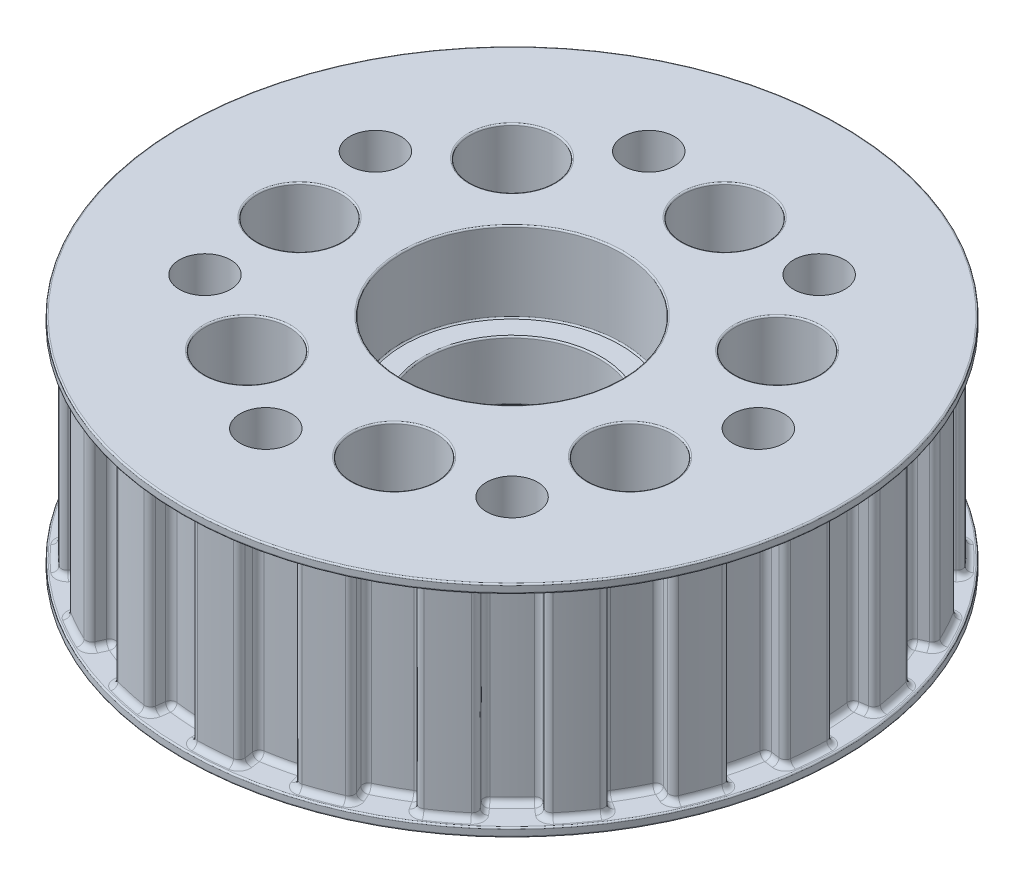
SolidWorks part; units mm, degrees
material "Aluminiumoxid"
ref_plane "Ebene vorne" through (0, 0, 0) normal (0, 0, 1) x (1, 0, 0)
ref_plane "Ebene oben" through (0, 0, 0) normal (0, 1, 0) x (1, 0, 0)
ref_plane "Ebene rechts" through (0, 0, 0) normal (1, 0, 0) x (0, 0, -1)
sketch "Skizze1" plane through (0, 0, 0) normal (0, 1, 0) x (1, 0, 0)
  circle A0 centre (0, 0) radius 45
  dimension "D1" = 90
extrude "Aufsatz-Linear austragen1" add sketch "Skizze1" along normal mid plane 30
sketch "Skizze2" plane through (0, 15, 0) normal (0, 1, 0) x (1, 0, 0)
  circle A0 centre (0, 0) radius 15
  dimension "D1" = 30
extrude "Schnitt-Linear austragen1" cut sketch "Skizze2" against normal blind 10.925
mirror "Spiegeln1" about plane through (0, 0, 0) normal (0, 1, 0) of "Schnitt-Linear austragen1"
sketch "Skizze3" plane through (0, -4.075, 0) normal (0, -1, 0) x (1, 0, 0)
  circle A0 centre (0, 0) radius 11.9
  dimension "D1" = 23.8
extrude "Schnitt-Linear austragen2" cut sketch "Skizze3" against normal through all
ref_plane "Ebene1" through (0, 13.8, 0) normal (0, 1, 0) x (1, 0, 0)
sketch "Skizze4" plane through (0, 13.8, 0) normal (0, 1, 0) x (1, 0, 0)
  line L0 (0, 0) -> (0, 50.5157) construction
  line L1 (0, 0) -> (7.4496, 51.8134) construction
  line L2 (0, 47.0395) -> (0, 41)
  line L3 (6.6944, 46.5607) -> (5.8349, 40.5827)
  arc A0 (5.8349, 40.5827) -> (0, 41) centre (0, 0) ccw
  circle A1 centre (0, 0) radius 45 construction
  arc A2 (6.6944, 46.5607) -> (0, 47.0395) centre (0, 0) ccw
  dimension "D1" = 8.182
  dimension "D2" = 4
extrude "Schnitt-Linear austragen3" cut sketch "Skizze4" against normal blind 27.6
pattern_circular "Kreismuster1" count 22 over 360 about axis through (0, 0, 0) along (0, 1, 0) of "Schnitt-Linear austragen3"
sketch "Skizze6" plane through (0, 13.8, 0) normal (0, 1, 0) x (1, 0, 0)
  circle A0 centre (0, 0) radius 55.1109
  circle A1 centre (0, 0) radius 43.8
  circle A2 centre (0, 0) radius 45 construction
  dimension "D1" = 110.2218
  dimension "D3" = 1.2
extrude "Schnitt-Linear austragen5" cut sketch "Skizze6" against normal blind 27.6
fillet "Verrundung1" radius 0.8 264 edges at (37.2949, 0, 17.032) (35.6691, -13.8, 22.9232) (35.6691, 13.8, 22.9232) (35.9848, 13.8, 19.6492) (35.9848, -13.8, 19.6492) (34.4914, 0, 22.1663) (30.9857, 0, 26.8493) (27.7661, -13.8, 32.0438) (27.7661, 13.8, 32.0438) (28.9914, 13.8, 28.9914) (28.9914, -13.8, 28.9914) (26.8493, 0, 30.9857) (22.1663, 0, 34.4914) (17.6136, -13.8, 38.5684) (17.6136, 13.8, 38.5684) (19.6492, 13.8, 35.9848) (19.6492, -13.8, 35.9848) (17.032, 0, 37.2949) (11.551, 0, 39.3392) (6.0341, -13.8, 41.9684) (6.0341, 13.8, 41.9684) (8.7152, 13.8, 40.063) (8.7152, -13.8, 40.063) (5.8349, 0, 40.5827) (0, 0, 41) (-6.0341, -13.8, 41.9684) (-6.0341, 13.8, 41.9684) (-2.9249, 13.8, 40.8955) (-2.9249, -13.8, 40.8955) (-5.8349, 0, 40.5827) (-11.551, 0, 39.3392) (-17.6136, -13.8, 38.5684) (-17.6136, 13.8, 38.5684) (-14.328, 13.8, 38.4149) (-14.328, -13.8, 38.4149) (-17.032, 0, 37.2949) (-22.1663, 0, 34.4914) (-27.7661, -13.8, 32.0438) (-27.7661, 13.8, 32.0438) (-24.5704, 13.8, 32.8222) (-24.5704, -13.8, 32.8222) (-26.8493, 0, 30.9857) (-30.9857, 0, 26.8493) (-35.6691, -13.8, 22.9232) (-35.6691, 13.8, 22.9232) (-32.8222, 13.8, 24.5704) (-32.8222, -13.8, 24.5704) (-34.4914, 0, 22.1663) (-37.2949, 0, 17.032) (-40.6825, -13.8, 11.9455) (-40.6825, 13.8, 11.9455) (-38.4149, 13.8, 14.328) (-38.4149, -13.8, 14.328) (-39.3392, 0, 11.551) (-40.5827, 0, 5.8349) (-42.4, -13.8, 0) (-42.4, 13.8, 0) (-40.8955, 13.8, 2.9249) (-40.8955, -13.8, 2.9249) (-41, 0, 0) (-40.5827, 0, -5.8349) (-40.6825, -13.8, -11.9455) (-40.6825, 13.8, -11.9455) (-40.063, 13.8, -8.7152) (-40.063, -13.8, -8.7152) (-39.3392, 0, -11.551) (-37.2949, 0, -17.032) (-35.6691, -13.8, -22.9232) (-35.6691, 13.8, -22.9232) (-35.9848, 13.8, -19.6492) (-35.9848, -13.8, -19.6492) (-34.4914, 0, -22.1663) (-30.9857, 0, -26.8493) (-27.7661, -13.8, -32.0438) (-27.7661, 13.8, -32.0438) (-28.9914, 13.8, -28.9914) (-28.9914, -13.8, -28.9914) (-26.8493, 0, -30.9857) (-22.1663, 0, -34.4914) (-17.6136, -13.8, -38.5684) (-17.6136, 13.8, -38.5684) (-19.6492, 13.8, -35.9848) (-19.6492, -13.8, -35.9848) (-17.032, 0, -37.2949) (37.2949, 0, -17.032) (40.6825, -13.8, -11.9455) (40.6825, 13.8, -11.9455) (38.4149, 13.8, -14.328) (38.4149, -13.8, -14.328) (39.3392, 0, -11.551) (30.9857, 0, -26.8493) (35.6691, -13.8, -22.9232) (35.6691, 13.8, -22.9232) (32.8222, 13.8, -24.5704) (32.8222, -13.8, -24.5704) (34.4914, 0, -22.1663) (22.1663, 0, -34.4914) (27.7661, -13.8, -32.0438) (27.7661, 13.8, -32.0438) (24.5704, 13.8, -32.8222) (24.5704, -13.8, -32.8222) (26.8493, 0, -30.9857) (11.551, 0, -39.3392) (17.6136, -13.8, -38.5684) (17.6136, 13.8, -38.5684) (14.328, 13.8, -38.4149) (14.328, -13.8, -38.4149) (17.032, 0, -37.2949) (-11.551, 0, -39.3392) (-6.0341, -13.8, -41.9684) (-6.0341, 13.8, -41.9684) (-8.7152, 13.8, -40.063) (-8.7152, -13.8, -40.063) (-5.8349, 0, -40.5827) (0, 0, -41) (6.0341, -13.8, -41.9684) (6.0341, 13.8, -41.9684) (2.9249, 13.8, -40.8955) (2.9249, -13.8, -40.8955) (5.8349, 0, -40.5827) (41.9684, 13.8, -6.0341) (41.9684, -13.8, -6.0341) (41.9684, 13.8, 6.0341) (41.9684, -13.8, 6.0341) (38.5684, 13.8, 17.6136) (38.5684, -13.8, 17.6136) (32.0438, 13.8, 27.7661) (32.0438, -13.8, 27.7661) (22.9232, 13.8, 35.6691) (22.9232, -13.8, 35.6691) (11.9455, 13.8, 40.6825) (11.9455, -13.8, 40.6825) (0, 13.8, 42.4) (0, -13.8, 42.4) (-11.9455, 13.8, 40.6825) (-11.9455, -13.8, 40.6825) (-22.9232, 13.8, 35.6691) (-22.9232, -13.8, 35.6691) (-32.0438, 13.8, 27.7661) (-32.0438, -13.8, 27.7661) (-38.5684, 13.8, 17.6136) (-38.5684, -13.8, 17.6136) (-41.9684, 13.8, 6.0341) (-41.9684, -13.8, 6.0341) (-41.9684, 13.8, -6.0341) (-41.9684, -13.8, -6.0341) (-38.5684, 13.8, -17.6136) (-38.5684, -13.8, -17.6136) (-32.0438, 13.8, -27.7661) (-32.0438, -13.8, -27.7661) (-22.9232, 13.8, -35.6691) (-22.9232, -13.8, -35.6691) (38.5684, 13.8, -17.6136) (38.5684, -13.8, -17.6136) (32.0438, 13.8, -27.7661) (32.0438, -13.8, -27.7661) (22.9232, 13.8, -35.6691) (22.9232, -13.8, -35.6691) (11.9455, 13.8, -40.6825) (11.9455, -13.8, -40.6825) (-11.9455, 13.8, -40.6825) (-11.9455, -13.8, -40.6825) (0, 13.8, -42.4) (0, -13.8, -42.4) (15.3065, -13.8, 41.0384) (26.2484, -13.8, 35.0637) (35.0637, -13.8, 26.2484) (41.0384, -13.8, 15.3065) (43.6884, -13.8, 3.1247) (42.799, -13.8, -9.3104) (38.4423, -13.8, -20.9911) (30.9713, -13.8, -30.9713) (20.9911, -13.8, -38.4423) (9.3104, -13.8, -42.799) (-3.1247, -13.8, -43.6884) (-15.3065, -13.8, -41.0384) (-26.2484, -13.8, -35.0637) (-35.0637, -13.8, -26.2484) (-41.0384, -13.8, -15.3065) (-43.6884, -13.8, -3.1247) (-42.799, -13.8, 9.3104) (-38.4423, -13.8, 20.9911) (-30.9713, -13.8, 30.9713) (-20.9911, -13.8, 38.4423) (-9.3104, -13.8, 42.799) (3.1247, -13.8, 43.6884) (-3.1247, 13.8, -43.6884) (9.3104, 13.8, -42.799) (-15.3065, 13.8, -41.0384) (0, 0, -43.8) (6.2334, 0, -43.3542) (-12.3399, 0, -42.0258) (-6.2334, 0, -43.3542) (20.9911, 13.8, -38.4423) (12.3399, 0, -42.0258) (18.1952, 0, -39.8419) (30.9713, 13.8, -30.9713) (23.6801, 0, -36.8469) (28.6829, 0, -33.1018) (38.4423, 13.8, -20.9911) (33.1018, 0, -28.6829) (36.8469, 0, -23.6801) (42.799, 13.8, -9.3104) (-26.2484, 13.8, -35.0637) (39.8419, 0, -18.1952) (42.0258, 0, -12.3399) (-35.0637, 13.8, -26.2484) (-23.6801, 0, -36.8469) (-18.1952, 0, -39.8419) (-41.0384, 13.8, -15.3065) (-33.1018, 0, -28.6829) (-28.6829, 0, -33.1018) (-43.6884, 13.8, -3.1247) (-39.8419, 0, -18.1952) (-36.8469, 0, -23.6801) (-42.799, 13.8, 9.3104) (-43.3542, 0, -6.2334) (-42.0258, 0, -12.3399) (-38.4423, 13.8, 20.9911) (-43.3542, 0, 6.2334) (-43.8, 0, 0) (-30.9713, 13.8, 30.9713) (-39.8419, 0, 18.1952) (-42.0258, 0, 12.3399) (-20.9911, 13.8, 38.4423) (-33.1018, 0, 28.6829) (-36.8469, 0, 23.6801) (-9.3104, 13.8, 42.799) (-23.6801, 0, 36.8469) (-28.6829, 0, 33.1018) (3.1247, 13.8, 43.6884) (-12.3399, 0, 42.0258) (-18.1952, 0, 39.8419) (15.3065, 13.8, 41.0384) (0, 0, 43.8) (-6.2334, 0, 43.3542) (26.2484, 13.8, 35.0637) (12.3399, 0, 42.0258) (6.2334, 0, 43.3542) (35.0637, 13.8, 26.2484) (23.6801, 0, 36.8469) (18.1952, 0, 39.8419) (41.0384, 13.8, 15.3065) (33.1018, 0, 28.6829) (28.6829, 0, 33.1018) (43.6884, 13.8, 3.1247) (39.8419, 0, 18.1952) (36.8469, 0, 23.6801) (43.3542, 0, 6.2334) (42.0258, 0, 12.3399) (43.3542, 0, -6.2334) (43.8, 0, 0) (40.5827, 0, -5.8349) (42.4, -13.8, 0) (42.4, 13.8, 0) (40.8955, 13.8, -2.9249) (40.8955, -13.8, -2.9249) (41, 0, 0) (40.5827, 0, 5.8349) (40.6825, -13.8, 11.9455) (40.6825, 13.8, 11.9455) (40.063, 13.8, 8.7152) (40.063, -13.8, 8.7152) (39.3392, 0, 11.551)
hole_wizard "Durchgangsloch für M101" positions "Skizze10" profile "Skizze9" hole size "M10" standard "DIN" end condition through all
sketch "Skizze10" plane through (0, 15, 0) normal (0, 1, 0) x (1, 0, 0)
  line L5 (-26.5165, 26.5165) -> (-10.6066, 10.6066) construction
  circle A0 centre (0, 0) radius 15
  circle A1 centre (0, 0) radius 37.5
  circle A2 centre (0, 0) radius 45 construction
  circle A3 centre (0, 0) radius 15 construction
  point P8 (-18.5616, 18.5616)
  point P50 (-18.5616, 18.5616)
  dimension "D1" = 7.5
sketch "Skizze9" plane through (-18.5616, 15, -18.5616) normal (1, 0, 0) x (0, 0, 1)
  line L0 (0, 0) -> (0, 30)
  line L1 (0, 30) -> (5.75, 30)
  line L2 (5.75, 30) -> (5.75, 0)
  line L5 (5.75, 0) -> (0, 0)
  line L11 (0, -6.35) -> (0, 107.95) construction
  dimension "Bohrerdurchmesser" = 11.5
  dimension "Bohrungstiefe" = 30
pattern_circular "Kreismuster3" count 7 over 360 about axis through (0, 0, 0) along (0, 1, 0) of "Durchgangsloch für M101"
fillet "Verrundung5" radius 0.2 24 edges at (0, -15, 45) (0, -15, 15) (-18.5616, -15, -12.8116) (-26.0849, -15, 8.6891) (-13.9658, -15, 27.9765) (8.6698, -15, 30.5269) (24.7769, -15, 14.4198) (22.2265, -15, -8.2158) (2.9391, -15, -20.3349) (0, -4.075, 15) (0, -4.075, -11.9) (0, 4.075, 15) (0, 4.075, 11.9) (0, 15, 45) (0, 15, 15) (-18.5616, 15, -12.8116) (-26.0849, 15, 8.6891) (-13.9658, 15, 27.9765) (8.6698, 15, 30.5269) (24.7769, 15, 14.4198) (22.2265, 15, -8.2158) (2.9391, 15, -20.3349) (0, 13.8, 45) (0, -13.8, 45)
hole_wizard "Durchgangsloch für M102" positions "Skizze13" profile "Skizze14" hole size "M10" standard "DIN" end condition through all
sketch "Skizze13" plane through (0, 15, 0) normal (0, 1, 0) x (1, 0, 0)
  line L2 (-18.5616, 18.5616) -> (-22.3232, 7.8112) construction
  line L3 (-22.3232, 7.8112) -> (-26.0849, -2.9391) construction
  line L5 (-35.0891, 12.2782) -> (-28.7062, 10.0447) construction
  line L6 (-28.7062, 10.0447) -> (-22.3232, 7.8112) construction
  circle A1 centre (0, 0) radius 37.3
  circle A2 centre (0, 0) radius 44.8 construction
  point P0 (-28.7062, 10.0447)
  dimension "D1" = 7.5
sketch "Skizze14" plane through (-28.7062, 15, -10.0447) normal (1, 0, 0) x (0, 0, 1)
  line L0 (0, 0) -> (0, 30)
  line L1 (0, 30) -> (3.5, 30)
  line L2 (3.5, 30) -> (3.5, 0)
  line L5 (3.5, 0) -> (0, 0)
  line L11 (0, -6.35) -> (0, 107.95) construction
  dimension "Bohrerdurchmesser" = 7
  dimension "Bohrungstiefe" = 30
pattern_circular "Kreismuster4" count 7 over 360 about axis through (0, 0, 0) along (0, 1, 0) of "Durchgangsloch für M102"
